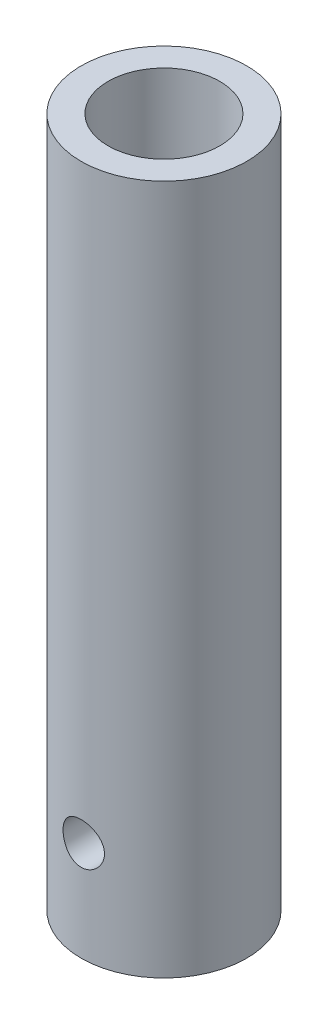
SolidWorks part; units mm, degrees
ref_plane "Front Plane" through (0, 0, 0) normal (0, 0, 1) x (1, 0, 0)
ref_plane "Top Plane" through (0, 0, 0) normal (0, 1, 0) x (1, 0, 0)
ref_plane "Right Plane" through (0, 0, 0) normal (1, 0, 0) x (0, 0, -1)
sketch "Sketch1" plane through (0, 0, 0) normal (0, 1, 0) x (1, 0, 0)
  circle A0 centre (0, 0) radius 6
  circle A1 centre (0, 0) radius 4.05
  dimension "D1" = 12
  dimension "D2" = 8.1
extrude "Boss-Extrude1" add sketch "Sketch1" along normal blind 50 contours A0
extrude "Cut-Extrude2" cut sketch "Sketch1<4>" against normal blind 15 from surface contours A1 starting at face at (0, 50, 6)
sketch "Sketch1<4>" plane through (0, 0, 0) normal (0, 1, 0) x (1, 0, 0) same geometry as "Sketch1"
sketch "Sketch3" plane through (0, 0, 0) normal (0, 0, 1) x (1, 0, 0)
  circle A0 centre (0, 7.2062) radius 1.5
extrude "Cut-Extrude3" cut sketch "Sketch3" against normal through all both and the other way through all
